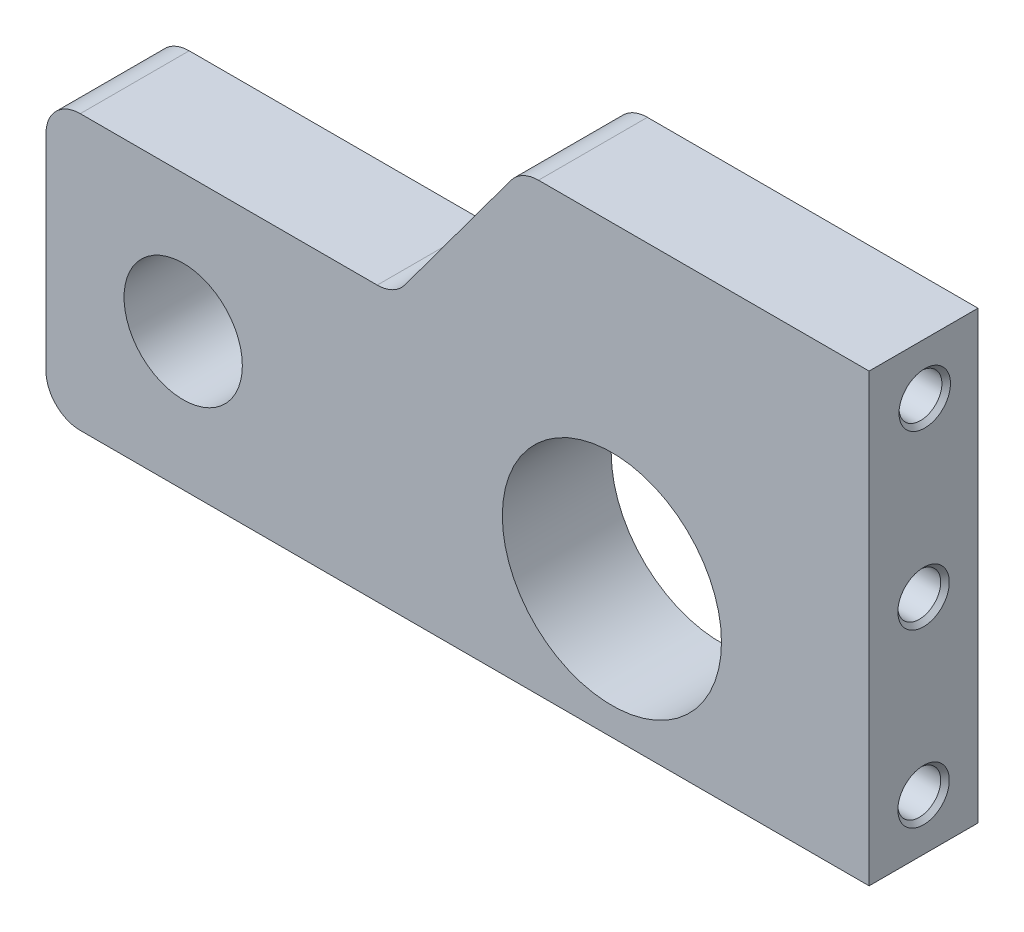
SolidWorks part; units mm, degrees
ref_plane "Front Plane" through (0, 0, 0) normal (0, 0, 1) x (1, 0, 0)
ref_plane "Top Plane" through (0, 0, 0) normal (0, 1, 0) x (1, 0, 0)
ref_plane "Right Plane" through (0, 0, 0) normal (1, 0, 0) x (0, 0, -1)
sketch "Sketch1" plane through (0, 0, 0) normal (0, 0, 1) x (1, 0, 0)
  line L0 (48, 8) -> (0, 8) construction
  line L1 (0, 0) -> (48, 0)
  line L2 (0, 0) -> (0, 16)
  line L3 (0, 16) -> (48, 16)
  line L4 (48, 0) -> (48, 16)
  circle A0 centre (8, 8) radius 3.45
  circle A1 centre (33, 8) radius 6.39
  dimension "D5" = 6.9
  dimension "D6" = 12.78
  dimension "D1" = 15
  dimension "D2" = 16
  dimension "D3" = 25
  dimension "D4" = 8
extrude "Boss-Extrude1" add sketch "Sketch1" along normal blind 6.35 contours L3 L4 L1 L2
extrude "Cut-Extrude1" cut sketch "Sketch1<6>" along normal blind 6.35 contours A0 L0 | L0 A0 | A1 region at (8, 6.5358, 0) region at (8, 9.4642, 0)
sketch "Sketch1<6>" plane through (0, 0, 0) normal (0, 0, 1) x (1, 0, 0) same geometry as "Sketch1"
fillet "Fillet1" radius 2 2 edges at (0, 16, 3.175) (0, 0, 3.175)
sketch "Sketch2" plane through (48, 0, 0) normal (1, 0, 0) x (0, 0, -1)
  line L0 (-6.35, 16) -> (0, 16) construction
  line L1 (-6.35, 0) -> (0, 0) construction
  line L4 (-6.35, 0) -> (-6.35, 16) construction
  circle A0 centre (-3.175, 13) radius 1.25
  circle A1 centre (-3.175, 3) radius 1.25
  dimension "D1" = 2.5
  dimension "D2" = 2.5
  dimension "D3" = 3
  dimension "D4" = 3
  dimension "D5" = 3.175
  dimension "D6" = 3.175
extrude "Cut-Extrude2" cut sketch "Sketch2" against normal blind 5
sketch "Sketch3" plane through (0, 0, 6.35) normal (0, 0, 1) x (1, 0, 0)
  line L0 (27.712, 26) -> (20.3263, 16)
  line L1 (48, 16) -> (27.712, 16)
  line L2 (48, 16) -> (48, 26)
  line L3 (48, 26) -> (27.712, 26)
  line L4 (27.712, 16) -> (27.712, 26)
  line L5 (2, 16) -> (48, 16) construction
  line M4 (48, 16) -> (2, 16)
  dimension "D1" = 10
extrude "Boss-Extrude2" add sketch "Sketch3" against normal blind 6.35 contours L4 L0 M4 | L4 L1 L2 L3 region at (25.2501, 19.3333, 6.35)
fillet "Fillet2" radius 2 2 edges at (20.3263, 16, 3.175) (27.712, 26, 3.175)
sketch "Sketch4" plane through (48, 0, 0) normal (1, 0, 0) x (0, 0, -1)
  line L0 (0, 26) -> (-6.35, 26) construction
  circle A0 centre (-3.1057, 23) radius 1.25
  dimension "D2" = 2.5
  dimension "D1" = 3
extrude "Cut-Extrude3" cut sketch "Sketch4" against normal blind 5
chamfer "Chamfer1" distance 0.25 angle 45 3 edges at (48, 3, 1.925) (48, 13, 1.925) (48, 23, 1.8557)
